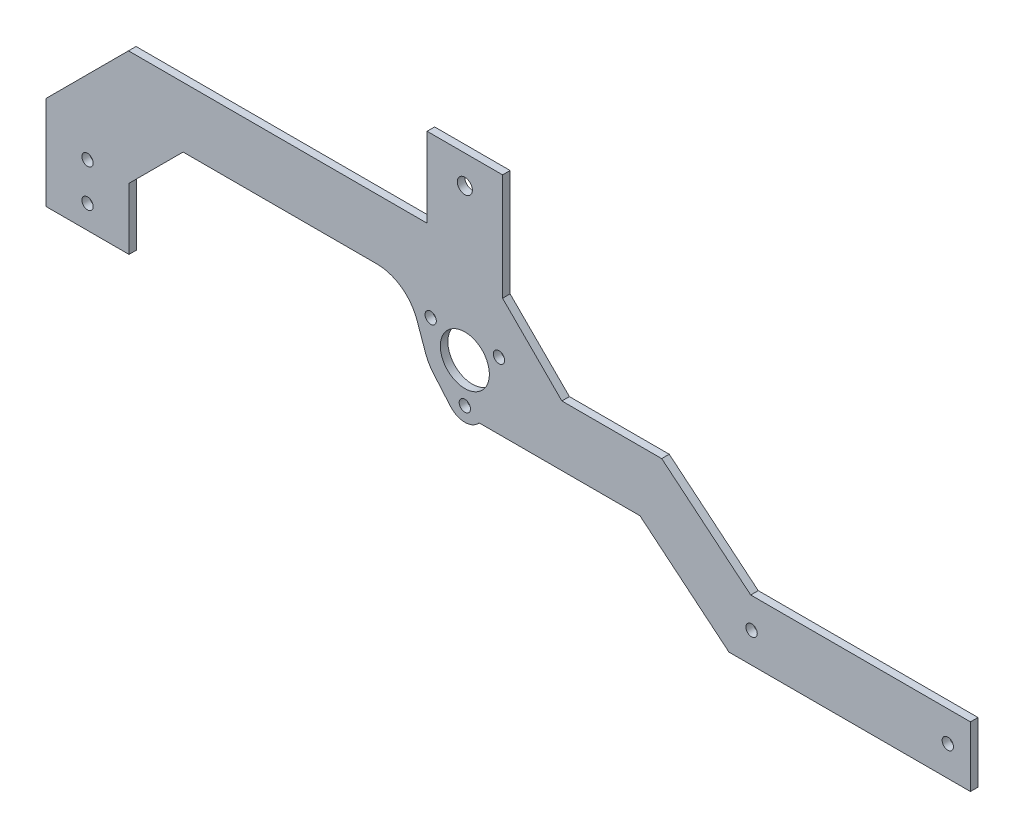
SolidWorks part; units mm, degrees
ref_plane "Спереди" through (0, 0, 0) normal (0, 0, 1) x (1, 0, 0)
ref_plane "Сверху" through (0, 0, 0) normal (0, 1, 0) x (1, 0, 0)
ref_plane "Справа" through (0, 0, 0) normal (1, 0, 0) x (0, 0, -1)
sketch "эскиз" plane through (0, 0, 0) normal (0, 0, 1) x (1, 0, 0)
  line L0 (110, -110) -> (110, -24) construction
  line L1 (-30, -110) -> (-30, -24) construction
  line L2 (-170, -24) -> (-136, -24) construction
  line L3 (-170, -110) -> (-30, -110) construction
  line L4 (-170, -24) -> (-188, -24) construction
  line L5 (-30, -110) -> (110, -110) construction
  line L6 (-170, -110) -> (-170, -24) construction
  line L7 (76, -24) -> (110, -24) construction
  line L8 (128, -24) -> (110, -24) construction
  line L9 (-42.5, -24) -> (-17.5, -24) construction
  line L10 (-170, -24) -> (-100, -24) construction
  line L11 (-100, -24) -> (-30, -24) construction
  line L12 (-100, -24) -> (0, 0) construction
  line L13 (0, 0) -> (110, -24) construction
  line L14 (-100, -24) -> (-100, -4) construction
  circle A0 centre (-170, -110) radius 57.5 construction
  circle A1 centre (-30, -110) radius 57.5 construction
  circle A2 centre (110, -110) radius 57.5 construction
  circle A3 centre (-188, -24) radius 1.5 construction
  circle A4 centre (-136, -24) radius 1.5 construction
  circle A5 centre (76, -24) radius 1.5 construction
  circle A6 centre (128, -24) radius 1.5 construction
  circle A7 centre (-42.5, -24) radius 1.5 construction
  circle A8 centre (-17.5, -24) radius 1.5 construction
  circle A9 centre (-100, -4) radius 1.5
  circle A10 centre (-100, -14) radius 1.5
  circle A11 centre (-100, -38) radius 2
  circle A12 centre (0, 40) radius 2
  point P31 (-153, -24)
  dimension "D1" = 115
  dimension "D4" = 3
  dimension "D7" = 25
  dimension "D12" = 3
  dimension "D11" = 4
  dimension "D17" = 4
  dimension "D2" = 140
  dimension "D3" = 86
  dimension "D5" = 18
  dimension "D6" = 34
  dimension "D8" = 70
  dimension "D9" = 280
  dimension "D10" = 30
  dimension "D13" = 10
  dimension "D14" = 14
  dimension "D15" = 110
  dimension "D16" = 10
  dimension "D18" = 40
sketch "эскиз 1" plane through (0, 0, 0) normal (0, 0, 1) x (1, 0, 0)
  line L0 (-194, -16) -> (-194, -32)
  line L1 (-194, -32) -> (-124, -32)
  line L2 (-124, -32) -> (-115.3397, -47)
  line L3 (-194, -16) -> (-115.9171, -16)
  line L4 (-115.9171, -16) -> (-109.5662, -27)
  line L5 (-11, -32) -> (-11, -16)
  line L6 (-115.3397, -47) -> (-84.6603, -47)
  line L9 (-109.5662, -27) -> (-90.4338, -27)
  line L10 (-76, -32) -> (-84.6603, -47)
  line L11 (-30, -16) -> (-30, -42) construction
  line L12 (-76, -32) -> (-11, -32)
  line L13 (-11, -32) -> (-76, -32)
  line L14 (-84.0829, -16) -> (-90.4338, -27)
  line L15 (-84.0829, -16) -> (-11, -16)
  line L16 (-100, -24) -> (-100, -4) construction
  line L17 (-30, -110) -> (-30, -24) construction
  line L18 (-170, -16) -> (-170, -32) construction
  line L19 (-170, -110) -> (-170, -24) construction
  line L20 (-170, -24) -> (-188, -24) construction
  line L21 (-100, -27) -> (-100, -47) construction
  circle A0 centre (-188, -24) radius 1.5
  circle A1 centre (-136, -24) radius 1.5
  circle A2 centre (-100, -36) radius 2
  circle A3 centre (-42.5, -24) radius 1.5
  circle A4 centre (-17.5, -24) radius 1.5
  circle A5 centre (-17.5, -24) radius 1.5 construction
  circle A6 centre (-42.5, -24) radius 1.5 construction
  circle A8 centre (-136, -24) radius 1.5 construction
  circle A9 centre (-188, -24) radius 1.5 construction
  point P11 (-100, -27)
  point P25 (-100, -47)
  dimension "D10" = 12
  dimension "D11" = 4
  dimension "D1" = 24
  dimension "D2" = 19
  dimension "D3" = 16
  dimension "D4" = 11
  dimension "D5" = 60
  dimension "D6" = 15
  dimension "D7" = 70
  dimension "D8" = 8
  dimension "D9" = 3
extrude "тело маленькой арки" [suppressed] add sketch "эскиз 1" along normal blind 2
sketch "Эскиз1" plane through (0, 0, 0) normal (0, 0, 1) x (1, 0, 0)
  line L0 (52.1733, 3.5068) -> (75.7592, -16)
  line L1 (75.7592, -16) -> (134, -16)
  line L2 (134, -16) -> (134, -32)
  line L3 (134, -32) -> (70, -32)
  line L4 (70, -32) -> (46.4141, -12.4932)
  line L5 (46.4141, -12.4932) -> (3.8054, -12.4932)
  line L6 (-111, -20.2244) -> (-111, 4.5822)
  line L7 (10, 19.2227) -> (10, 47.5464)
  line L8 (-74.6646, 10.4416) -> (-23.333, 10.4416)
  line L9 (52.1733, 3.5068) -> (25.716, 3.5068)
  line L10 (-12.7222, 2.951) -> (-10.3652, -3.6828)
  line L12 (-8.9167, 9.5422) -> (-1.9932, 10.8179) construction
  line L13 (110, -110) -> (110, -24) construction
  line L14 (3.8054, -12.4932) -> (8.372, -7.1351) construction
  line L15 (-3.8054, -12.4932) -> (-8.372, -7.1351)
  line L16 (-111, -20.2244) -> (-89, -20.2244)
  line L17 (-89, -3.8938) -> (-74.6646, 10.4416)
  line L18 (-100, -4) -> (-100, -20.2244) construction
  line L19 (-100, -24) -> (-100, -4) construction
  line L20 (8.9167, 9.5422) -> (1.9932, 10.8179) construction
  line L21 (-89, -20.2244) -> (-89, -3.8938)
  line L22 (10, 47.5464) -> (-10, 47.5464)
  line L23 (10, 19.2227) -> (25.716, 3.5068)
  line L24 (-10, 47.5464) -> (-10, 26.4416)
  line L25 (-111, 4.5822) -> (-89.1406, 26.4416)
  line L26 (-89.1406, 26.4416) -> (-10, 26.4416)
  line L27 (12.7222, 2.951) -> (10.3652, -3.6828) construction
  circle A0 centre (-100, -14) radius 1.5
  circle A1 centre (-100, -4) radius 1.5
  circle A2 centre (-100, -4) radius 1.5 construction
  circle A3 centre (-100, -14) radius 1.5 construction
  circle A4 centre (0, 0) radius 6.5
  circle A5 centre (0, 0) radius 11 construction
  arc A6 (-8.9167, 9.5422) -> (-12.7222, 2.951) centre (-8.0107, 4.625) ccw construction
  arc A7 (1.9932, 10.8179) -> (-1.9932, 10.8179) centre (0, 0) ccw construction
  arc A8 (-3.8054, -12.4932) -> (3.8054, -12.4932) centre (0, -9.25) ccw
  arc A9 (12.7222, 2.951) -> (8.9167, 9.5422) centre (8.0107, 4.625) ccw construction
  arc A10 (8.372, -7.1351) -> (10.3652, -3.6828) centre (0, 0) ccw construction
  arc A11 (-10.3652, -3.6828) -> (-8.372, -7.1351) centre (0, 0) ccw
  circle A12 centre (0, 0) radius 9.25 construction
  circle A13 centre (0, -10.45) radius 1.5
  circle A14 centre (-9.05, 5.225) radius 1.5
  circle A15 centre (9.05, 5.225) radius 1.5
  circle A16 centre (0, 0) radius 7.65 construction
  circle A17 centre (128, -24) radius 1.5
  circle A18 centre (76, -24) radius 1.5
  circle A19 centre (76, -24) radius 1.5 construction
  circle A20 centre (128, -24) radius 1.5 construction
  circle A21 centre (0, 40) radius 2
  circle A22 centre (0, 40) radius 2 construction
  arc A23 (-12.7222, 2.951) -> (-23.333, 10.4416) centre (-23.333, -0.819) ccw
  point P27 (134, -24)
  point P33 (0, 47.5464)
  point P50 (38.2697, 3.5068)
  point P62 (0, 0)
  point P68 (0, 0)
  point P81 (0, 0)
  point P82 (0, 0)
  dimension "D2" = 13
  dimension "D3" = 3
  dimension "D5" = 5
  dimension "D6" = 18.5
  dimension "D7" = 22
  dimension "D14" = 3
  dimension "D17" = 15.3
  dimension "D18" = 45
  dimension "D20" = 20
  dimension "D13" = 16
  dimension "D1" = 16
  dimension "D4" = 16
  dimension "D8" = 11
  dimension "D9" = 6
  dimension "D10" = 24
  dimension "D11" = 135
  dimension "D12" = 16
  dimension "D15" = 3
  dimension "D16" = 11
  dimension "D19" = 10.45
extrude "тело большой арки" add sketch "Эскиз1" along normal blind 2
